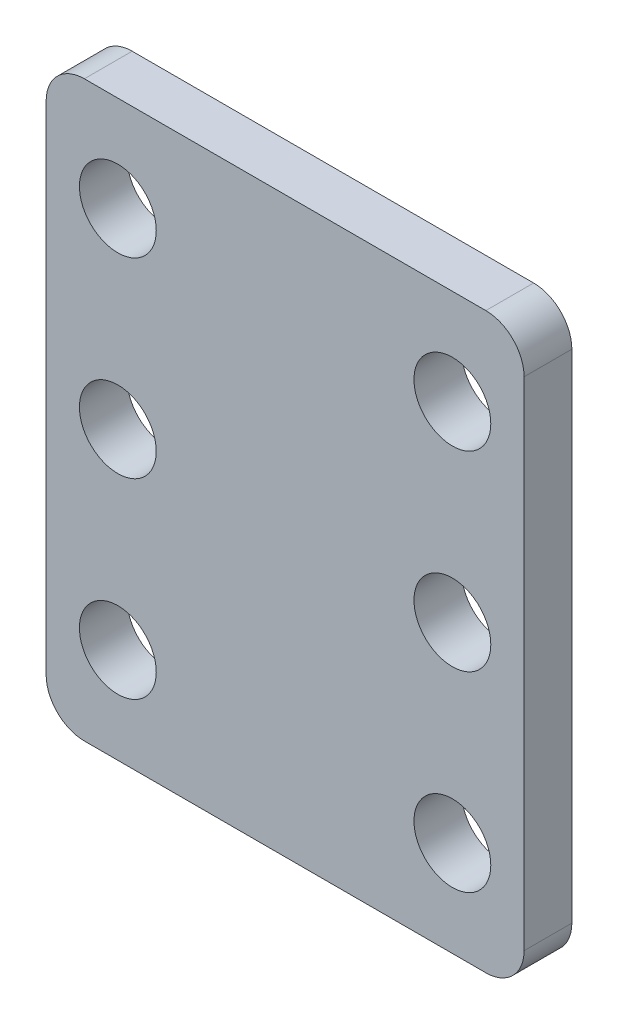
SolidWorks part; units mm, degrees
material "6061-T6 (SS)"
ref_plane "Front Plane" through (0, 0, 0) normal (0, 0, 1) x (1, 0, 0)
ref_plane "Top Plane" through (0, 0, 0) normal (0, 1, 0) x (1, 0, 0)
ref_plane "Right Plane" through (0, 0, 0) normal (1, 0, 0) x (0, 0, -1)
sketch "Sketch1" plane through (0, 0, 0) normal (0, 0, 1) x (1, 0, 0)
  line L1 (-15.875, -19.05) -> (15.875, -19.05)
  line L2 (-15.875, -19.05) -> (-15.875, 19.05)
  line L3 (-15.875, 19.05) -> (15.875, 19.05)
  line L4 (15.875, -19.05) -> (15.875, 19.05)
  line L5 (-15.875, -19.05) -> (15.875, 19.05) construction
  line L6 (-15.875, 19.05) -> (15.875, -19.05) construction
  line L11 (-10.5833, -12.7) -> (6.2596, 7.5116) construction
  line L13 (-11.1125, 12.7) -> (11.1125, 12.7) construction
  line L14 (-11.1125, 12.7) -> (-11.1125, -12.7) construction
  line L15 (-11.1125, -12.7) -> (11.1125, -12.7) construction
  line L16 (11.1125, 12.7) -> (11.1125, -12.7) construction
  circle A3 centre (-11.1125, 12.7) radius 2.5527
  circle A4 centre (-11.1125, 0) radius 2.5527
  circle A5 centre (11.1125, 12.7) radius 2.5527
  circle A6 centre (11.1125, -12.7) radius 2.5527
  circle A7 centre (11.1125, 0) radius 2.5527
  circle A8 centre (-11.1125, -12.7) radius 2.5527
  point P0 (0, 0)
  point P6 (0, 0)
  point P13 (0, 12.7)
  dimension "D2" = 12.7
  dimension ".201" = 5.1054
  dimension "D4" = 12.7
  dimension "D1" = 38.1
  dimension "D3" = 31.75
  dimension "1" = 22.225
extrude "Boss-Extrude1" add sketch "Sketch1" along normal blind 3.175
fillet "Fillet1" radius 2.54 4 edges at (-15.875, 19.05, 1.5875) (-15.875, -19.05, 1.5875) (15.875, -19.05, 1.5875) (15.875, 19.05, 1.5875)
